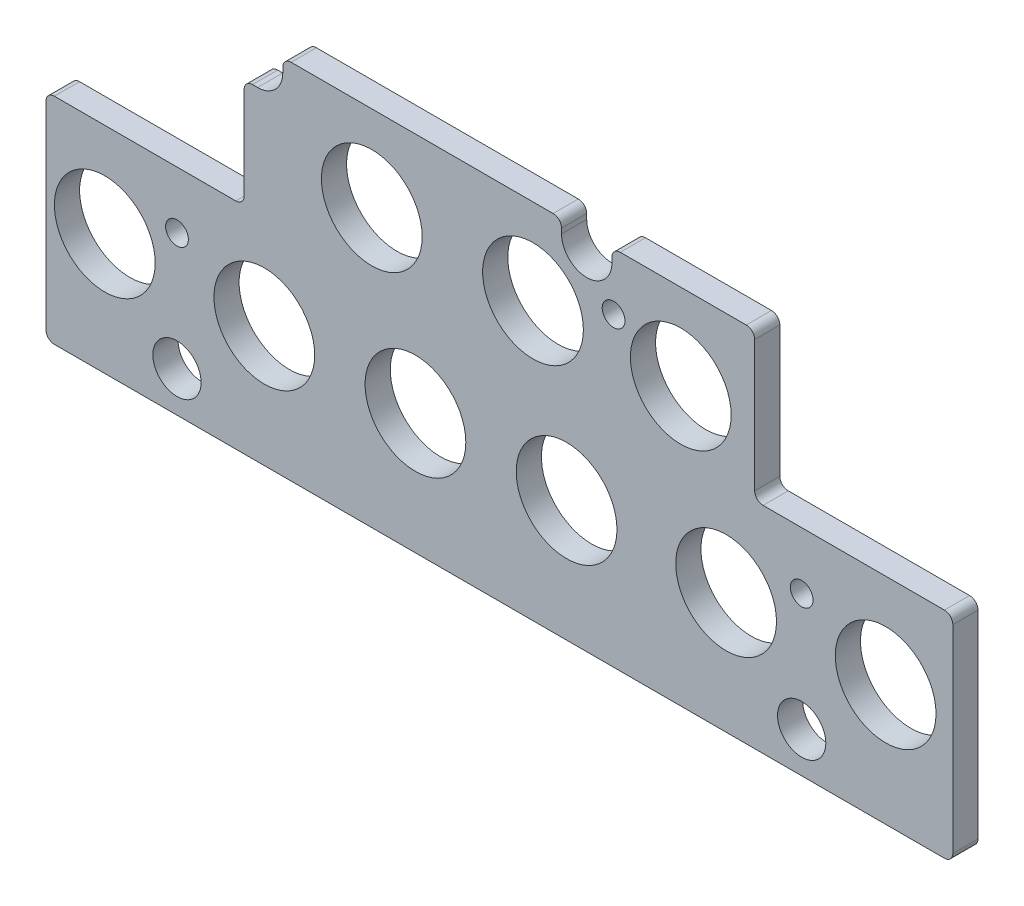
SolidWorks part; units mm, degrees
material "Acrylic (Medium-high impact)"
ref_plane "Front Plane" through (0, 0, 0) normal (0, 0, 1) x (1, 0, 0)
ref_plane "Top Plane" through (0, 0, 0) normal (0, 1, 0) x (1, 0, 0)
ref_plane "Right Plane" through (0, 0, 0) normal (1, 0, 0) x (0, 0, -1)
sketch "Sketch1" plane through (0, 0, 0) normal (0, 0, 1) x (1, 0, 0)
  line L13 (-40.9575, 29.8102) -> (-40.9575, 27.2702)
  line L14 (-45.72, 22.5077) -> (-48.26, 22.5077)
  line L15 (-48.26, 22.5077) -> (-48.26, 1.8702)
  line L16 (-48.26, 1.8702) -> (-85.725, 1.8702)
  line L17 (-85.725, 1.8702) -> (-85.725, -38.7698)
  line L18 (-85.725, -38.7698) -> (85.725, -38.7698)
  line L19 (85.725, -38.7698) -> (85.725, 1.8702)
  line L20 (85.725, 1.8702) -> (48.26, 1.8702)
  line L21 (48.26, 1.8702) -> (48.26, 29.8102)
  line L22 (48.26, 29.8102) -> (21.2725, 29.8102)
  line L23 (21.2725, 29.8102) -> (21.2725, 27.2702)
  line L24 (11.7475, 27.2702) -> (11.7475, 29.8102)
  line L25 (11.7475, 29.8102) -> (-40.9575, 29.8102)
  line L26 (-40.9575, 29.8102) -> (-40.9575, 27.2702)
  line L27 (-45.72, 22.5077) -> (-48.26, 22.5077)
  line L28 (-48.26, 22.5077) -> (-48.26, 1.8702)
  line L29 (-48.26, 1.8702) -> (-85.725, 1.8702)
  line L30 (-85.725, 1.8702) -> (-85.725, -38.7698)
  line L31 (-85.725, -38.7698) -> (85.725, -38.7698)
  line L32 (85.725, -38.7698) -> (85.725, 1.8702)
  line L33 (85.725, 1.8702) -> (48.26, 1.8702)
  line L34 (48.26, 1.8702) -> (48.26, 29.8102)
  line L35 (48.26, 29.8102) -> (21.2725, 29.8102)
  line L36 (21.2725, 29.8102) -> (21.2725, 27.2702)
  line L37 (11.7475, 27.2702) -> (11.7475, 29.8102)
  line L38 (11.7475, 29.8102) -> (-40.9575, 29.8102)
  arc A2 (-45.72, 22.5077) -> (-40.9575, 27.2702) centre (-45.72, 27.2702) ccw
  arc A3 (11.7475, 27.2702) -> (21.2725, 27.2702) centre (16.51, 27.2702) ccw
  arc A4 (-45.72, 22.5077) -> (-40.9575, 27.2702) centre (-45.72, 27.2702) ccw
  arc A5 (11.7475, 27.2702) -> (21.2725, 27.2702) centre (16.51, 27.2702) ccw
  dimension "D1" = 0
extrude "Boss-Extrude1" add sketch "Sketch1" along normal blind 4.7625
sketch "Sketch3" plane through (0, 0, 4.7625) normal (0, 0, 1) x (1, 0, 0)
  circle A0 centre (73.025, -15.9098) radius 9.525
  circle A1 centre (42.8625, -15.9098) radius 9.525
  circle A2 centre (12.7, -15.9098) radius 9.525
  circle A3 centre (-15.875, -15.9098) radius 9.525
  circle A4 centre (-44.45, -15.9098) radius 9.525
  circle A5 centre (-74.6125, -15.9098) radius 9.525
  circle A6 centre (34.29, 13.6177) radius 9.525
  circle A7 centre (6.35, 13.6177) radius 9.525
  circle A8 centre (-24.13, 13.6177) radius 9.525
  dimension "D1" = 19.05
extrude "Cut-Extrude1" cut sketch "Sketch3" against normal through all
hole_wizard "#6 Clearance Hole1" positions "Sketch5" profile "Sketch4" hole size "#6" standard "ANSI Inch" end condition through all
sketch "Sketch5" plane through (0, 0, 4.7625) normal (0, 0, 1) x (1, 0, 0)
  point P3 (57.15, -8.9248)
  point P8 (21.59, 19.0152)
  point P11 (-60.96, -8.9248)
sketch "Sketch4" plane through (57.15, -8.9248, 4.7625) normal (1, 0, 0) x (0, -1, 0)
  line L0 (0, 0) -> (0, 4.7625)
  line L1 (0, 4.7625) -> (2.1526, 4.7625)
  line L2 (2.1526, 4.7625) -> (2.1526, 0)
  line L5 (2.1526, 0) -> (0, 0)
  line L11 (0, -6.35) -> (0, 107.95) construction
  dimension "Thru Hole Dia." = 4.3053
  dimension "Thru Hole Depth" = 4.7625
hole_wizard "23/64 (0.35938) Diameter Hole1" positions "Sketch7" profile "Sketch6" hole size "23/64" standard "ANSI Inch" end condition through all
sketch "Sketch7" plane through (0, 0, 4.7625) normal (0, 0, 1) x (1, 0, 0)
  point P0 (57.15, -31.1498)
  point P3 (-60.96, -31.1498)
sketch "Sketch6" plane through (57.15, -31.1498, 4.7625) normal (1, 0, 0) x (0, -1, 0)
  line L0 (0, 0) -> (0, 4.7625)
  line L1 (0, 4.7625) -> (4.5641, 4.7625)
  line L2 (4.5641, 4.7625) -> (4.5641, 0)
  line L5 (4.5641, 0) -> (0, 0)
  line L11 (0, -6.35) -> (0, 107.95) construction
  dimension "Thru Hole Dia." = 9.1283
  dimension "Thru Hole Depth" = 4.7625
fillet "Fillet1" radius 1.5875 11 edges at (85.725, -38.7698, 2.3813) (-85.725, -38.7698, 2.3813) (85.725, 1.8702, 2.3813) (48.26, 1.8702, 2.3813) (48.26, 29.8102, 2.3813) (21.2725, 29.8102, 2.3813) (11.7475, 29.8102, 2.3813) (-40.9575, 29.8102, 2.3813) (-48.26, 22.5077, 2.3813) (-48.26, 1.8702, 2.3813) (-85.725, 1.8702, 2.3813)
